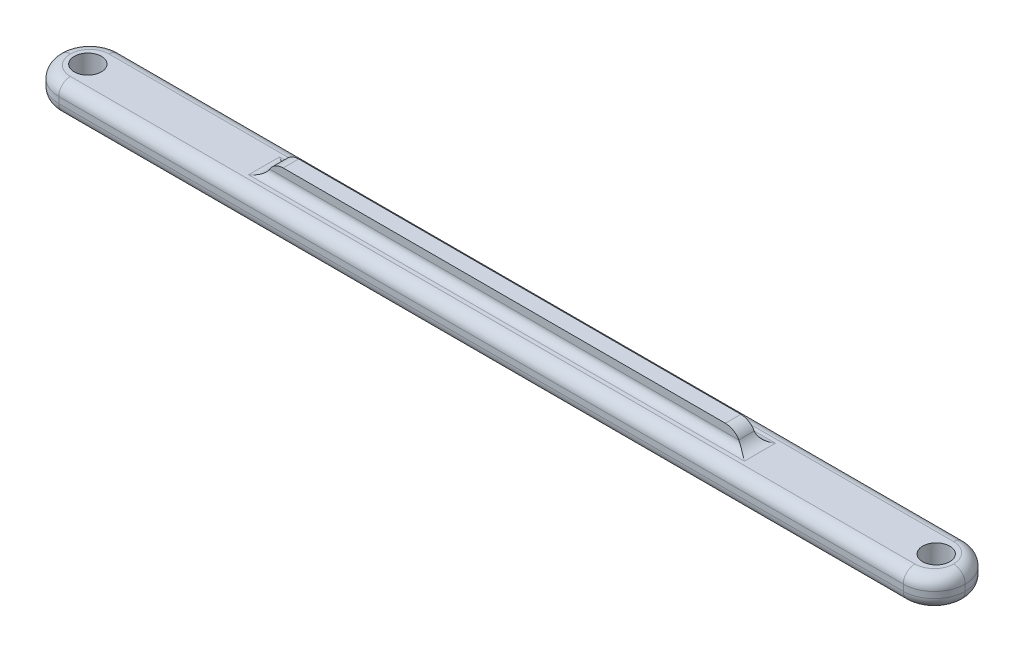
SolidWorks part; units mm, degrees
material "ABS"
ref_plane "Front Plane" through (0, 0, 0) normal (0, 0, 1) x (1, 0, 0)
ref_plane "Top Plane" through (0, 0, 0) normal (0, 1, 0) x (1, 0, 0)
ref_plane "Right Plane" through (0, 0, 0) normal (1, 0, 0) x (0, 0, -1)
sketch "Sketch1" plane through (0, 0, 0) normal (0, 1, 0) x (1, 0, 0)
  line L1 (-58.5, 4) -> (58.5, 4)
  line L2 (-58.5, 4) -> (-58.5, -4)
  line L3 (-58.5, -4) -> (58.5, -4)
  line L4 (58.5, 4) -> (58.5, -4)
  line L5 (-58.5, 4) -> (58.5, -4) construction
  line L6 (-58.5, -4) -> (58.5, 4) construction
  point P0 (0, 0)
  dimension "D1" = 8
  dimension "D2" = 117
extrude "Boss-Extrude1" add sketch "Sketch1" along normal blind 3.8
sketch "Sketch2" plane through (0, 3.8, 0) normal (0, 1, 0) x (1, 0, 0)
  line L0 (0, 0) -> (-54.75, 0) construction
  line L1 (0, 0) -> (54.75, 0) construction
  line L3 (-58.5, 4) -> (-58.5, -4) construction
  line L4 (58.5, -4) -> (58.5, 4) construction
  circle A0 centre (-54.75, 0) radius 1.75
  circle A1 centre (54.75, 0) radius 1.75
  dimension "D3" = 3.5
  dimension "D4" = 3.5
  dimension "D1" = 3.75
  dimension "D2" = 3.75
extrude "Cut-Extrude4" cut sketch "Sketch2" against normal through all
fillet "Fillet1" radius 4 4 edges at (58.5, 1.9, -4) (58.5, 1.9, 4) (-58.5, 1.9, 4) (-58.5, 1.9, -4)
fillet "Fillet2" radius 1.5 12 edges at (57.3284, 0, -2.8284) (57.3284, 0, 2.8284) (0, 0, 4) (-57.3284, 0, 2.8284) (-57.3284, 0, -2.8284) (57.3284, 3.8, -2.8284) (57.3284, 3.8, 2.8284) (0, 3.8, 4) (-57.3284, 3.8, 2.8284) (-57.3284, 3.8, -2.8284) (0, 0, -4) (0, 3.8, -4)
sketch "Sketch3" plane through (0, 3.8, 0) normal (0, 1, 0) x (1, 0, 0)
  line L1 (-30, 1) -> (30, 1)
  line L2 (-30, 1) -> (-30, -1)
  line L3 (-30, -1) -> (30, -1)
  line L4 (30, 1) -> (30, -1)
  line L5 (-30, 1) -> (30, -1) construction
  line L6 (-30, -1) -> (30, 1) construction
  point P0 (0, 0)
  dimension "D1" = 60
  dimension "D2" = 2
extrude "Boss-Extrude2" add sketch "Sketch3" along normal blind 2 and the other way blind 5.8
fillet "Fillet3" radius 2 4 edges at (-30, 0, 0) (30, 0, 0) (-30, 3.8, 0) (30, 3.8, 0)
fillet "Fillet4" radius 2 4 edges at (-30, 5.8, 0) (-30, -2, 0) (30, -2, 0) (30, 5.8, 0)
fillet "Fillet5" radius 1 4 edges at (0, 3.8, -1) (0, 3.8, 1) (0, 0, 1) (0, 0, -1)
